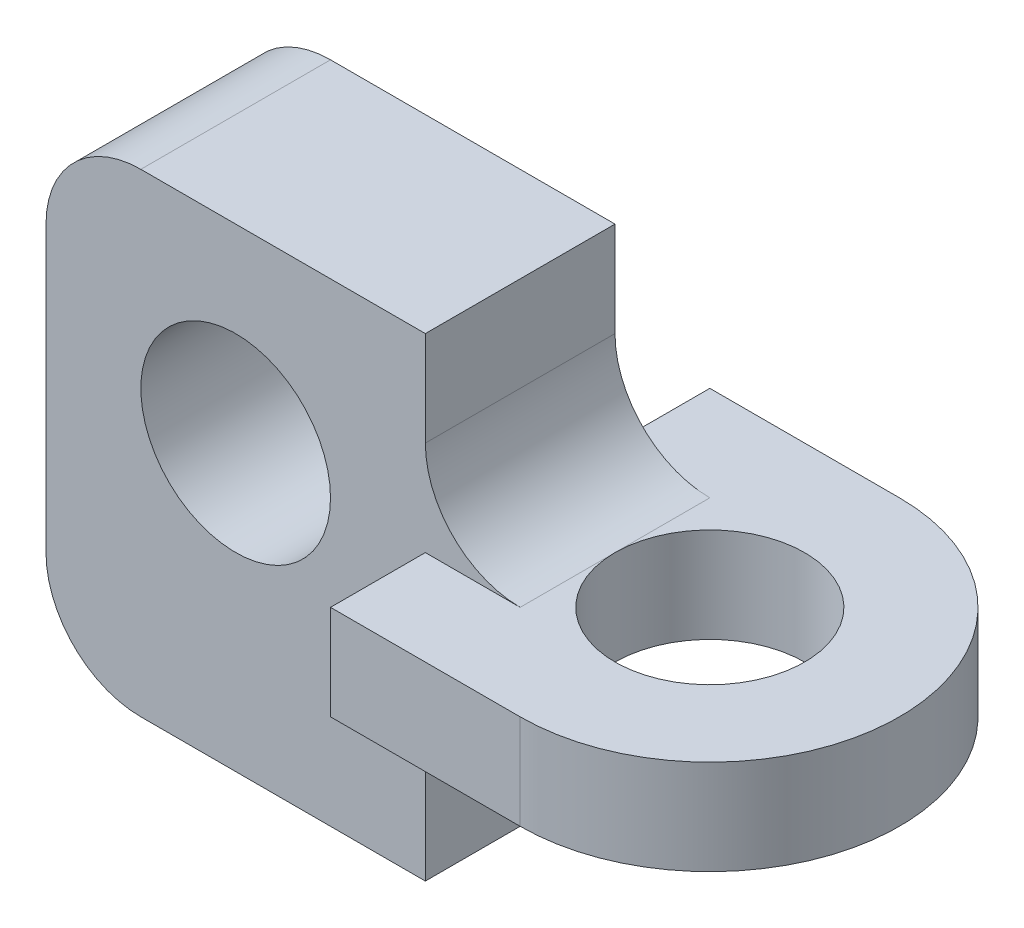
SolidWorks part; units mm, degrees
ref_plane "前基準面" through (0, 0, 0) normal (0, 0, 1) x (1, 0, 0)
ref_plane "上基準面" through (0, 0, 0) normal (0, 1, 0) x (1, 0, 0)
ref_plane "右基準面" through (0, 0, 0) normal (1, 0, 0) x (0, 0, -1)
sketch "草圖1" plane through (0, 0, 0) normal (0, 0, 1) x (1, 0, 0)
  line L1 (-10, 10) -> (10, 10)
  line L2 (-10, 10) -> (-10, -15)
  line L3 (-10, -15) -> (10, -15)
  line L4 (10, 10) -> (10, -15)
  circle A0 centre (0, 0) radius 5
  dimension "D1" = 10
  dimension "D2" = 10
  dimension "D3" = 10
  dimension "D4" = 25
  dimension "D5" = 20
extrude "填料-伸長1" add sketch "草圖1" along normal mid plane 10 contours L2 L3 L4 L1
ref_plane "平面1" through (0, -2.5, 0) normal (0, 1, 0) x (1, 0, 0)
sketch "草圖2" plane through (0, -2.5, 0) normal (0, 1, 0) x (1, 0, 0)
  line L1 (10, -5) -> (10, 5) construction
  line L2 (20, 10) -> (10, 10)
  line L4 (20, -10) -> (10, -10)
  line L5 (10, 10) -> (10, -10)
  arc A0 (20, 10) -> (20, -10) centre (20, 0) cw
  circle A1 centre (20, 0) radius 5
  point P6 (10, 0)
  point P10 (10, 0)
  dimension "D2" = 10
  dimension "D4" = 10
  dimension "D1" = 20
  dimension "D3" = 10
extrude "填料-伸長2" add sketch "草圖2" along normal mid plane 5
fillet "圓角1" radius 5 4 edges at (-10, -15, 0) (-10, 10, 0) (10, -5, 0) (10, 0, 0)
